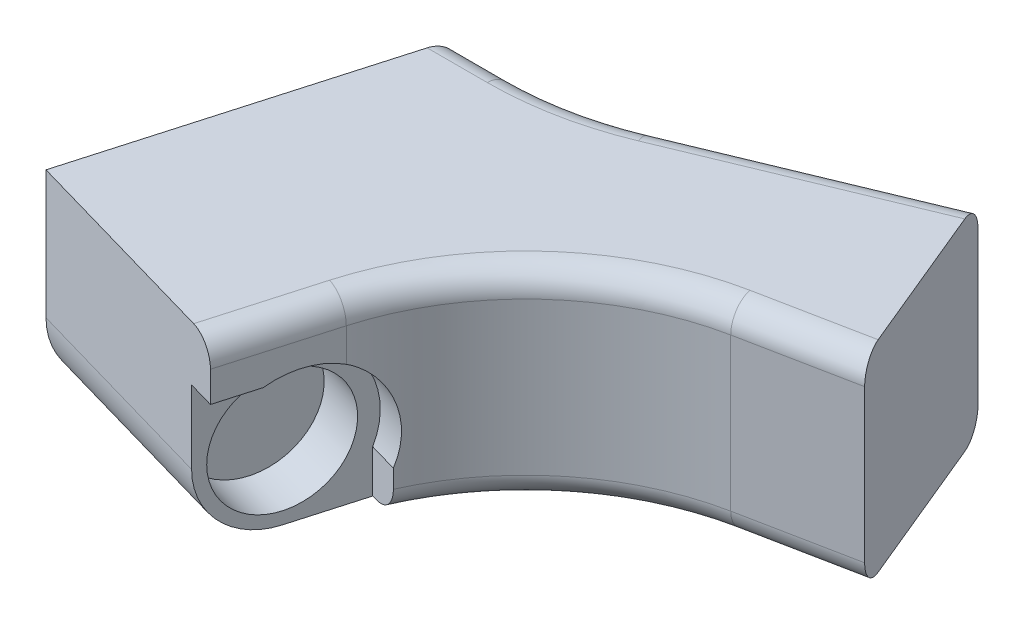
SolidWorks part; units mm, degrees
ref_plane "Спереди" through (0, 0, 0) normal (0, 0, 1) x (1, 0, 0)
ref_plane "Сверху" through (0, 0, 0) normal (0, 1, 0) x (1, 0, 0)
ref_plane "Справа" through (0, 0, 0) normal (1, 0, 0) x (0, 0, -1)
sketch "Эскиз2" plane through (0, 0, 0) normal (0, 1, 0) x (1, 0, 0)
  line L0 (-37.0181, 71.2336) -> (-60.5171, 61.5)
  line L1 (-69.8478, 61.5) -> (-60.5171, 61.5)
  line L3 (-53.9856, 37.3604) -> (-49.6599, 36.12)
  line L4 (-49.6599, 36.12) -> (-50.3578, 33.6863)
  line L5 (-50.3578, 33.6863) -> (-54.6834, 34.9267)
  line L17 (-62.1563, 39.7033) -> (-61.1916, 43.0677)
  line L24 (-61.1916, 43.0677) -> (-57.3465, 41.9652)
  line L25 (-57.3465, 41.9652) -> (-60.6542, 30.43)
  line L26 (-20.9839, 57.3097) -> (-21.1984, 57.2209)
  line L28 (-17, 57.5) -> (-17.2322, 57.5)
  line L30 (-60.6542, 30.43) -> (-64.4992, 31.5326)
  line L31 (-75.5193, 43.5351) -> (-75.0386, 43.3973)
  line L32 (-75.0386, 43.3973) -> (-74.0739, 46.7617)
  line L34 (-39.6579, 36.893) -> (-40.6226, 33.5286)
  line L35 (-74.0739, 46.7617) -> (-70.2289, 45.6591)
  line L36 (-37.2122, 54.0355) -> (-37.1146, 53.5451) construction
  line L37 (-55.8479, 29.0519) -> (-52.5402, 40.587)
  line L39 (-37.1146, 53.5451) -> (-52.0151, 50.5813)
  line L41 (-39.1205, 24.2554) -> (-42.9655, 25.3579)
  line L43 (-39.6579, 36.893) -> (-35.8129, 35.7905)
  line L45 (-40.6226, 33.5286) -> (-42.0008, 28.7223)
  line L46 (-42.0008, 28.7223) -> (-42.9655, 25.3579)
  line L47 (-39.1205, 24.2554) -> (-38.1558, 27.6198)
  line L49 (-38.1558, 27.6198) -> (-36.7776, 32.4261)
  line L51 (-36.7776, 32.4261) -> (-35.8129, 35.7905)
  line L52 (-36.7776, 32.4261) -> (-40.6226, 33.5286)
  line L53 (-42.0008, 28.7223) -> (-38.1558, 27.6198)
  line L54 (-26.4853, 38.5) -> (-35.0359, 38.5)
  line L55 (-35.8129, 35.7905) -> (-35.0359, 38.5)
  line L56 (-78, 34.8837) -> (-75.5193, 43.5351)
  line L57 (-71.1936, 42.2947) -> (-78, 44.2464)
  line L59 (-70.2289, 45.6591) -> (-73.5365, 34.124)
  line L60 (-73.5365, 34.124) -> (-77.3816, 35.2265)
  line L62 (-75.0386, 43.3973) -> (-76.4168, 38.5909)
  line L63 (-76.4168, 38.5909) -> (-72.5718, 37.4884)
  line L64 (-76.4168, 38.5909) -> (-77.3816, 35.2265)
  line L65 (-74.0739, 46.7617) -> (-69.8478, 61.5)
  line L66 (-70.7314, 58.4185) -> (-71.212, 58.5563) construction
  line L67 (-71.212, 58.5563) -> (-70.3679, 61.5)
  line L68 (-70.3679, 61.5) -> (-78, 61.5)
  line L69 (-71.212, 58.5563) -> (-75.5193, 43.5351)
  line L70 (-64.4992, 31.5326) -> (-62.1563, 39.7033)
  line L71 (-54.6834, 34.9267) -> (-53.9856, 37.3604)
  line L73 (-51.6069, 36.6783) -> (-51.6035, 36.6902)
  line L74 (-51.6035, 36.6902) -> (-55.6644, 37.8547)
  line L75 (-48.6952, 39.4844) -> (-52.0028, 27.9493)
  line L77 (-52.0028, 27.9493) -> (-55.8479, 29.0519)
  line L83 (-73.5365, 34.124) -> (-64.4992, 31.5326)
  line L84 (-56.145, 37.9925) -> (-52.4581, 50.8502)
  line L85 (-52.0028, 27.9493) -> (-42.9655, 25.3579)
  line L86 (-55.6644, 37.8547) -> (-52.0151, 50.5813)
  line L87 (-56.145, 37.9925) -> (-58.3078, 38.6127)
  line L88 (-26.4853, 55.6595) -> (-26.4853, 38.5)
  line L89 (-37.0181, 71.2336) -> (-30.4515, 55.3803)
  line L91 (-52.5402, 40.587) -> (-48.6952, 39.4844)
  line L93 (-37.2122, 54.0355) -> (-21.1984, 57.2209)
  line L94 (-37.2122, 54.0355) -> (-52.4117, 51.0122)
  line L95 (-52.4581, 50.8502) -> (-52.4117, 51.0122)
  line L96 (-37.1146, 53.5451) -> (-17.2322, 57.5)
  point P8 (0, 0)
  point P9 (0, 0)
  point P23 (0, 0)
  point P30 (0, 0)
  point P31 (0, 0)
  point P32 (0, 0)
  point P33 (0, 0)
  point P38 (0, 0)
  point P39 (0, 0)
  point P40 (0, 0)
  point P41 (0, 0)
  point P42 (0, 0)
  point P43 (0, 0)
  point P44 (0, 0)
  point P46 (0, 0)
  point P47 (0, 0)
  point P49 (0, 0)
  point P50 (0, 0)
  point P51 (0, 0)
  point P52 (0, 0)
  point P54 (-75.5193, 43.5351)
  point P63 (0, 0)
  point P64 (0, 0)
  point P73 (0, 0)
  point P76 (0, 0)
  point P77 (0, 0)
  point P81 (0, 0)
  point P82 (0, 0)
  point P84 (0, 0)
  point P85 (0, 0)
  point P86 (0, 0)
  point P87 (0, 0)
  point P91 (0, 0)
sketch "Эскиз3" plane through (0, 0, 0) normal (0, 1, 0) x (1, 0, 0)
  line L0 (-30.4515, 55.3803) -> (-37.0181, 71.2336)
  line L1 (-37.0181, 71.2336) -> (-60.5171, 61.5)
  line L2 (-60.5171, 61.5) -> (-69.8478, 61.5)
  line L3 (-69.8478, 61.5) -> (-77.3816, 35.2265)
  line L4 (-77.3816, 35.2265) -> (-73.5365, 34.124)
  line L5 (-73.5365, 34.124) -> (-70.2289, 45.6591)
  line L6 (-70.2289, 45.6591) -> (-61.1916, 43.0677)
  line L7 (-61.1916, 43.0677) -> (-64.4992, 31.5326)
  line L8 (-64.4992, 31.5326) -> (-60.6542, 30.43)
  line L22 (-56.145, 37.9925) -> (-52.4581, 50.8502) construction
  line L23 (-56.0106, 38.4612) -> (-58.4913, 29.8099)
  line L24 (-60.6542, 30.43) -> (-58.4913, 29.8099)
  line L28 (-37.2122, 54.0355) -> (-52.4117, 51.0122) construction
  line L29 (-30.4515, 55.3803) -> (-39.6058, 53.5594)
  arc A4 (-56.0106, 38.4612) -> (-39.6058, 53.5594) centre (-35.4286, 32.5594) cw
extrude "Бобышка-Вытянуть1" add sketch "Эскиз3" against normal blind 6 and the other way blind 10.5 contours L0 L1 L2 L3 L4 L5 L6 L7 L8 region at (-54.8741, 0, -53.1919)
fillet "Скругление1" radius 25 1 edges at (-60.5171, 2.25, -61.5)
fillet "Скругление2" radius 2 12 edges at (-67.6688, 10.5, -61.5) (-60.6126, 10.5, -61.9804) (-67.6688, -6, -61.5) (-60.6126, -6, -61.9804) (-46.4705, 10.5, -67.3183) (-46.4705, -6, -67.3183) (-57.251, -6, -34.1355) (-35.0287, -6, -54.4699) (-57.251, 10.5, -34.1355) (-35.0287, 10.5, -54.4699) (-49.9284, -6, -48.314) (-49.9284, 10.5, -48.314)
sketch "Эскиз4" plane through (-67.9537, 0, -19.4854) normal (0.9613, 0, 0.2756) x (0.2756, 0, -0.9613)
  line L0 (12.5327, -6) -> (18.5327, -6)
  line L2 (18.5327, -6) -> (18.5327, 0)
  line L3 (12.5327, 0) -> (12.5327, -6)
  line L4 (12.5327, -6) -> (18.5327, -6)
  circle A0 centre (18.5327, 0) radius 5
  circle A1 centre (18.5327, 0) radius 6
  line M17 (24.5327, -6) -> (12.5327, -6)
  line M18 (12.5327, -6) -> (12.5327, 10.5)
extrude "Вырез-Вытянуть1" cut sketch "Эскиз4" against normal through all and the other way blind 4 contours A0 | A1 M18 M17 region at (-64.1298, -4.6598, -32.8209) region at (-63.7924, 3.4355, -33.9977)
sketch "Эскиз5" plane through (-61.9458, 0, -17.7627) normal (0.9613, 0, 0.2756) x (0.2756, 0, -0.9613)
  line L0 (12.5327, -6) -> (12.5327, 0)
  line L1 (12.5327, 8.5) -> (12.5327, -4) construction
  line L3 (36.6593, 0) -> (21.0327, 0) construction
  line L4 (16.0327, 6) -> (12.5327, 6)
  line L5 (12.5327, 6) -> (12.5327, 0)
  line L6 (12.5327, -6) -> (18.5327, -6)
  line L9 (24.5327, -6) -> (18.5327, -6)
  line L10 (24.5327, -2.5) -> (24.5327, -6)
  arc A2 (24.5327, -2.5) -> (16.0327, 6) centre (18.5327, 0) ccw
  point P8 (0, 0)
  line M1 (12.5327, 8.5) -> (12.5327, -4)
  line M3 (21.5327, -4) -> (21.5327, 8.5)
extrude "Вырез-Вытянуть2" cut sketch "Эскиз5" against normal blind 2.25 and the other way through all contours L6 | L5 M1 | A2 L4 M3 M1 | L10 A2 L9 M3 region at (-56.8608, -0.0843, -35.4964)
sketch "Эскиз6" plane through (-67.9537, 0, -19.4854) normal (-0.9613, 0, -0.2756) x (-0.2756, 0, 0.9613)
  line L0 (-16.0327, 0) -> (-21.0327, 0) construction
  line L1 (-24.5327, 10.5) -> (-24.5327, -6)
  line L2 (-24.5327, -6) -> (-18.5327, -6)
  line L4 (-12.5327, 0) -> (-12.5327, 10.5)
  line L5 (-12.5327, 10.5) -> (-24.5327, 10.5)
  arc A0 (-18.5327, -6) -> (-12.5327, 0) centre (-18.5327, 0) ccw
extrude "Бобышка-Вытянуть2" add sketch "Эскиз6" along normal up to surface (9.4015 mm away) up to face at (-73.2609, 0, -35.0852)
